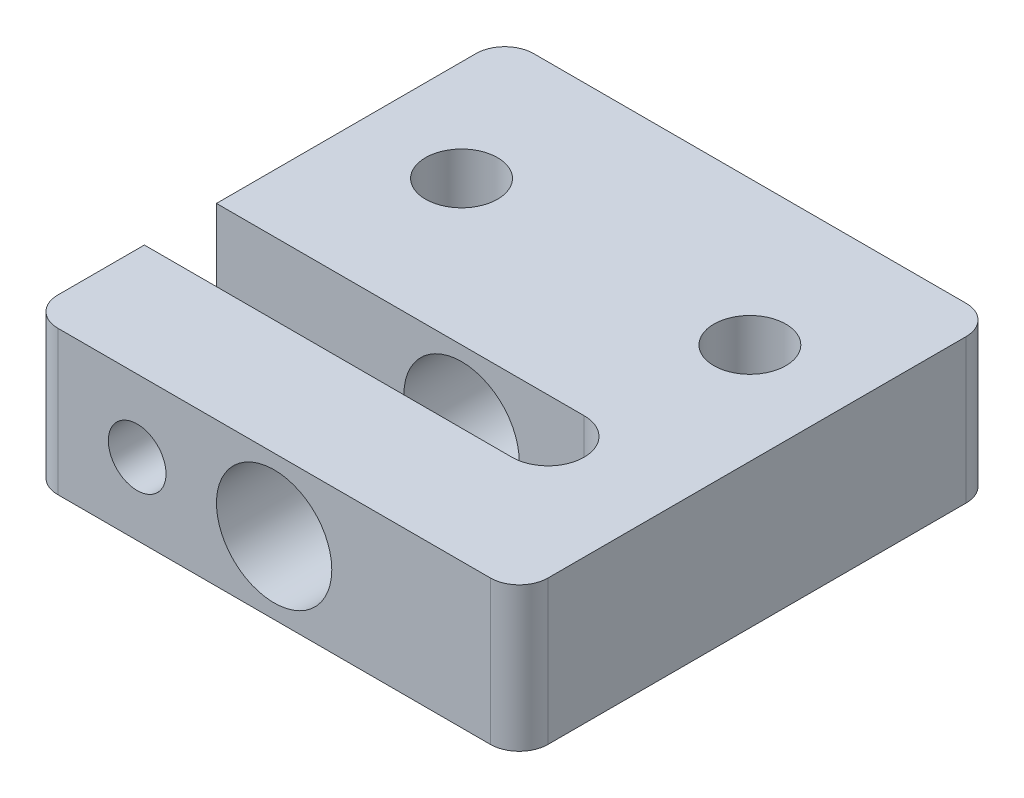
SolidWorks part; units mm, degrees
ref_plane "Front Plane" through (0, 0, 0) normal (0, 0, 1) x (1, 0, 0)
ref_plane "Top Plane" through (0, 0, 0) normal (0, 1, 0) x (1, 0, 0)
ref_plane "Right Plane" through (0, 0, 0) normal (1, 0, 0) x (0, 0, -1)
sketch "Sketch2" plane through (0, 0, 0) normal (0, 1, 0) x (1, 0, 0)
  line L1 (0, 0) -> (34, 0)
  line L2 (0, 0) -> (0, 33)
  line L3 (0, 33) -> (34, 33)
  line L4 (34, 0) -> (34, 33)
  dimension "D1" = 33
  dimension "D2" = 34
extrude "Boss-Extrude1" add sketch "Sketch2" along normal blind 10
fillet "Fillet1" radius 2 1 edges at (34, 5, 0) type face fillet first side face at (17, 5, 0) second side face at (34, 5, -16.5)
fillet "Fillet2" radius 2 1 edges at (34, 5, -33) type face fillet first side face at (34, 5, -17.5) second side face at (17, 5, -33)
fillet "Fillet3" radius 2 1 edges at (0, 5, -33) type face fillet first side face at (16, 5, -33) second side face at (0, 5, -16.5)
fillet "Fillet4" radius 2 1 edges at (0, 5, 0) type face fillet first side face at (0, 5, -15.5) second side face at (16, 5, 0)
sketch "Sketch3" plane through (0, 10, 0) normal (0, 1, 0) x (1, 0, 0)
  line L0 (32, 33) -> (2, 33) construction
  line L1 (0, 31) -> (0, 2) construction
  line L2 (34, 2) -> (34, 31) construction
  circle A0 centre (7, 23) radius 2.5
  circle A1 centre (27, 23) radius 2.5
  dimension "D3" = 5
  dimension "D4" = 5
  dimension "D1" = 10
  dimension "D2" = 7
  dimension "D5" = 7
extrude "Cut-Extrude1" cut sketch "Sketch3" against normal blind 10
sketch "Sketch4" plane through (0, 10, 0) normal (0, 1, 0) x (1, 0, 0)
  line L0 (0, 31) -> (0, 2) construction
  line L2 (0, 13) -> (28, 13)
  line L3 (0, 13) -> (0, 8)
  line L4 (0, 8) -> (28, 8)
  line L5 (28, 13) -> (28, 8)
  line L6 (2, 0) -> (32, 0) construction
  dimension "D1" = 5
  dimension "D2" = 28
  dimension "D3" = 8
extrude "Cut-Extrude2" cut sketch "Sketch4" against normal blind 10
fillet "Fillet5" radius 2.5 1 edges at (28, 5, -13) type face fillet first side face at (14, 5, -13) second side face at (28, 5, -10.5)
fillet "Fillet6" radius 2.5 1 edges at (28, 5, -8) type face fillet first side face at (28, 5, -9.25) second side face at (14, 5, -8)
sketch "Sketch5" plane through (0, 0, 0) normal (0, 0, 1) x (1, 0, 0)
  circle A0 centre (17, 5) radius 4
  dimension "D1" = 8
extrude "Cut-Extrude3" cut sketch "Sketch5" against normal blind 60
sketch "Sketch6" plane through (0, 0, 0) normal (0, 0, 1) x (1, 0, 0)
  line L0 (0, 0) -> (0, 10) construction
  circle A0 centre (7.5, 5) radius 2
  point P2 (0, 0)
  dimension "D1" = 4
  dimension "D2" = 7.5
extrude "Cut-Extrude4" cut sketch "Sketch6" against normal blind 10
